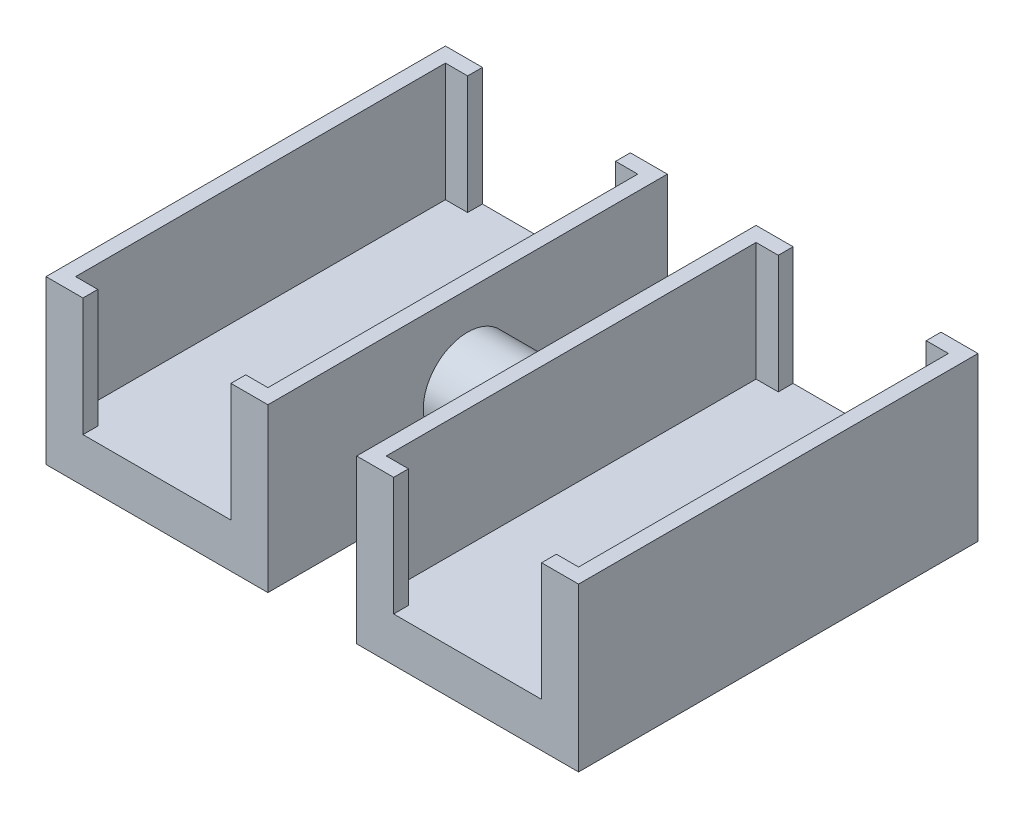
SolidWorks part; units mm, degrees
material "PBT General Purpose"
ref_plane "Front Plane" through (0, 0, 0) normal (0, 0, 1) x (1, 0, 0)
ref_plane "Top Plane" through (0, 0, 0) normal (0, 1, 0) x (1, 0, 0)
ref_plane "Right Plane" through (0, 0, 0) normal (1, 0, 0) x (0, 0, -1)
sketch "Base Reference Sketch" plane through (0, 0, 0) normal (0, 1, 0) x (1, 0, 0)
  line L0 (-18, 13.5) -> (-15.5, 13.5)
  line L5 (-15.5, 13.5) -> (-15.5, 12.5)
  line L6 (-15.5, 12.5) -> (-17, 12.5)
  line L7 (-17, -12.5) -> (-15.5, -12.5)
  line L8 (-15.5, -12.5) -> (-15.5, -13.5)
  line L9 (-16.5, 12) -> (-4.5, 12) construction
  line L10 (-16.5, 12) -> (-16.5, -12) construction
  line L11 (-16.5, -12) -> (-4.5, -12) construction
  line L12 (-4.5, 12) -> (-4.5, -12) construction
  line L13 (-16.5, 12) -> (-4.5, -12) construction
  line L14 (-16.5, -12) -> (-4.5, 12) construction
  line L19 (-17, 12.5) -> (-4, 12.5) construction
  line L20 (-4, 12.5) -> (-4, -12.5)
  line L21 (-17, -12.5) -> (-4, -12.5) construction
  line L22 (-17, 12.5) -> (-17, -12.5)
  line L23 (-18, 13.5) -> (-3, 13.5) construction
  line L24 (-3, 13.5) -> (-3, -13.5)
  line L25 (-18, -13.5) -> (-3, -13.5) construction
  line L26 (-18, 13.5) -> (-18, -13.5)
  line L27 (-15.5, -13.5) -> (-18, -13.5)
  line L44 (-3, 13.5) -> (-5.5, 13.5)
  line L45 (-5.5, 13.5) -> (-5.5, 12.5)
  line L46 (-5.5, 12.5) -> (-4, 12.5)
  line L47 (-4, -12.5) -> (-5.5, -12.5)
  line L48 (-5.5, -12.5) -> (-5.5, -13.5)
  line L49 (-5.5, -13.5) -> (-3, -13.5)
  line L51 (-15.5, -13.5) -> (-5.5, -13.5) construction
  line L52 (-15.5, -13.5) -> (-15.5, 13.5) construction
  line L53 (-15.5, 13.5) -> (-5.5, 13.5) construction
  line L54 (-5.5, -13.5) -> (-5.5, 13.5) construction
  line L55 (-15.5, -13.5) -> (-5.5, 13.5) construction
  line L56 (-15.5, 13.5) -> (-5.5, -13.5) construction
  line L96 (-18, 13.5) -> (0, 13.5)
  line L97 (-18, 13.5) -> (-18, -13.5)
  line L98 (-18, -13.5) -> (0, -13.5)
  line L99 (0, 13.5) -> (0, -13.5)
  point P0 (-10.5, 0)
  point P2 (-10.5, 0)
  point P4 (0, 0)
  point P5 (-10.5, 0)
  point P6 (-10.5, 0)
  point P11 (0, 0)
  point P28 (-10.5, 0)
  point P40 (0, 0)
  point P47 (-16.5, 12)
  dimension "D1" = 24
  dimension "D2" = 3
  dimension "D3" = 1.5
  dimension "D6" = 12
  dimension "D4" = 0.5
  dimension "D5" = 10
extrude "Base Extrude" add sketch "Base Reference Sketch" along normal blind 3 contours L27 L8 L7 L22 L6 L5 L0 L26 | L48 L49 L24 L44 L45 L46 L20 L47 | L8 L98 L48 L47 L20 L46 L45 L96 L5 L6 L22 L7
extrude "Boss-Extrude2" add sketch "Base Reference Sketch<5>" along normal blind 8 from surface contours L20 L47 L48 L49 L24 L44 L45 L46 | L22 L7 L8 L27 L26 L0 L5 L6 starting at face at (-10.5, 3, 0)
sketch "Base Reference Sketch<5>" plane through (0, 0, 0) normal (0, 1, 0) x (1, 0, 0) same geometry as "Base Reference Sketch"
mirror "Mirror2" about plane through (0, 0, 0) normal (1, 0, 0) of bodies 106
sketch "Sketch1" plane through (0, 0, 0) normal (1, 0, 0) x (0, 0, -1)
  line L0 (13.5, 5.5) -> (0, 5.5) construction
  line L1 (13.5, 11) -> (13.5, 0) construction
  circle A0 centre (0, 5.5) radius 3
  circle A1 centre (0, 5.5) radius 1.5
  point P4 (0, 0)
  dimension "D1" = 3
  dimension "D2" = 6
extrude "Boss-Extrude4" add sketch "Sketch1" along normal up to next (3 mm away) and the other way up to next (3 mm away)
